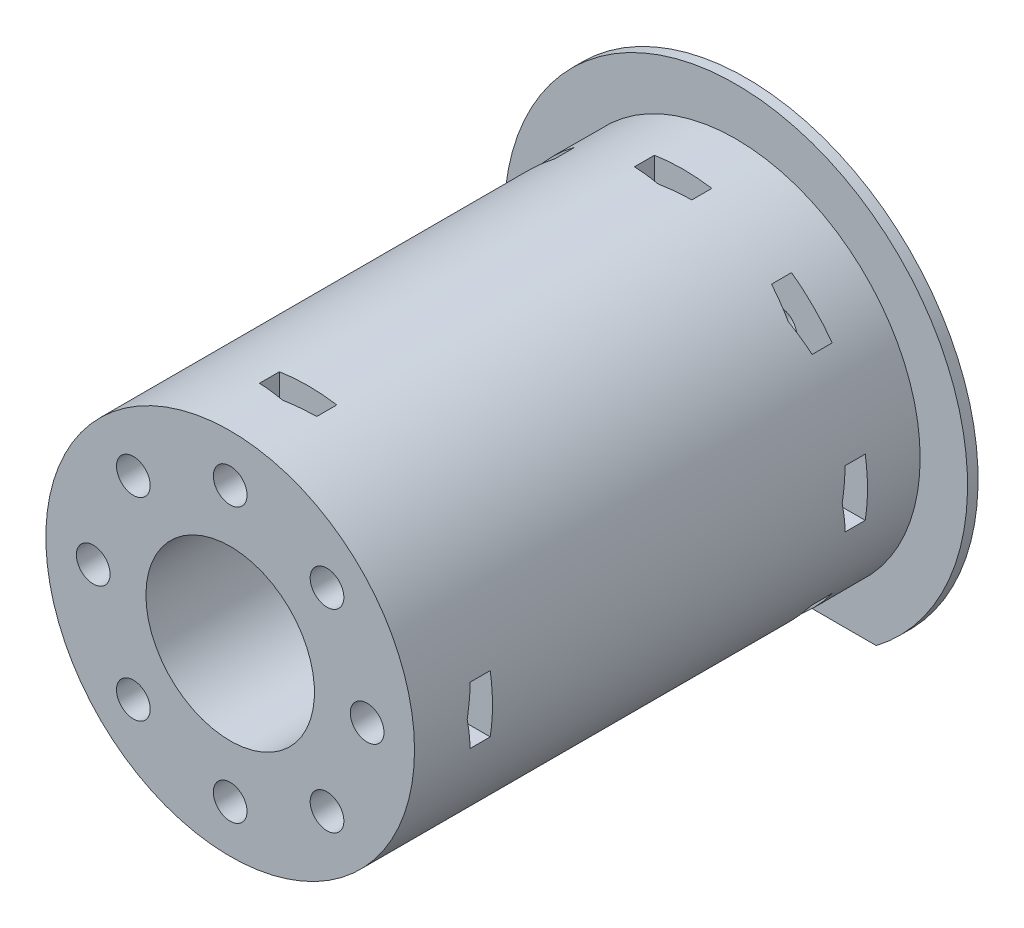
SolidWorks part; units mm, degrees
ref_plane "Front Plane" through (0, 0, 0) normal (1, 0, 0) x (0, 1, 0)
ref_plane "Top Plane" through (0, 0, 0) normal (0, 0, 1) x (0, 1, 0)
ref_plane "Right Plane" through (0, 0, 0) normal (0, 1, 0) x (-1, 0, 0)
sketch "Sketch1" plane through (0, 0, 0) normal (0, 0, 1) x (0, 1, 0)
  circle A0 centre (0, 0) radius 17.5
  dimension "D1" = 35
extrude "Boss-Extrude1" add sketch "Sketch1" along normal blind 24 and the other way blind 24
sketch "Sketch3" plane through (0, 0, -24) normal (0, 0, -1) x (1, 0, 0)
  circle A0 centre (0, 0) radius 22
  dimension "D1" = 44
extrude "Boss-Extrude2" add sketch "Sketch3" along normal blind 1
sketch "Sketch2" plane through (0, 0, 24) normal (0, 0, 1) x (1, 0, 0)
  line L0 (-2.725, 15.725) -> (-2.725, 17.2865)
  line L2 (-2.725, 15.725) -> (-2.725, 10.275)
  line L3 (-2.725, 10.275) -> (2.725, 10.275)
  line L4 (2.725, 15.725) -> (2.725, 10.275)
  line L5 (-2.725, 15.725) -> (2.725, 10.275) construction
  line L6 (-2.725, 10.275) -> (2.725, 15.725) construction
  line L7 (2.725, 15.725) -> (2.725, 17.2865)
  circle A0 centre (0, 0) radius 13 construction
  circle A1 centre (0, 13) radius 1.6
  circle A2 centre (0, 0) radius 17.5 construction
  arc A3 (-2.725, 17.2865) -> (2.725, 17.2865) centre (0, 0) cw
  dimension "D1" = 26
  dimension "D4" = 3.2
  dimension "D2" = 5.45
  dimension "D3" = 5.45
extrude "Cut-Extrude1" cut sketch "Sketch2" against normal through all contours A1
extrude "Cut-Extrude2" cut sketch "Sketch2<4>" against normal blind 2.4 from offset 5 offset against normal yes
sketch "Sketch2<4>" plane through (0, 0, 24) normal (0, 0, 1) x (1, 0, 0) same geometry as "Sketch2"
extrude "Cut-Extrude3" cut sketch "Sketch2<5>" along normal blind 2.4 from offset 43 offset against normal yes
sketch "Sketch2<5>" plane through (0, 0, 24) normal (0, 0, 1) x (1, 0, 0) same geometry as "Sketch2"
chamfer "Chamfer1" distance 2.725 distance2 0.5 2 edges at (-2.725, 13.7808, 19) (2.725, 13.7808, 19) first distance on face at (1.6, 13, 19)
chamfer "Chamfer2" distance 2.725 distance2 0.5 2 edges at (-2.725, 13.7808, -16.6) (2.725, 13.7808, -16.6) first distance on face at (0, 13.8341, -16.6)
pattern_circular "CirPattern1" count 4 over 360 about axis through (0, 0, -24) along (0, 0, 1) of "Cut-Extrude2", "Chamfer1" reverse direction yes
pattern_circular "CirPattern3" count 8 over 360 about axis through (0, 0, -24) along (0, 0, 1) of "Cut-Extrude3", "Chamfer2", "Cut-Extrude1"
sketch "Sketch4" plane through (0, 0, -25) normal (0, 0, -1) x (1, 0, 0)
  circle A0 centre (0, 0) radius 8
  dimension "D1" = 16
extrude "Cut-Extrude4" cut sketch "Sketch4" against normal through all both and the other way through all
sketch "Sketch5" plane through (0, 0, -25) normal (0, 0, -1) x (1, 0, 0)
  line L0 (-0.5, -10) -> (-0.5, -0.5)
  line L1 (-10, 0.5) -> (-0.5, 0.5)
  line L2 (-10, 0.5) -> (-10, -0.5)
  line L3 (-10, -0.5) -> (-0.5, -0.5)
  line L4 (10, 0.5) -> (10, -0.5)
  line L5 (-10, 0.5) -> (10, -0.5) construction
  line L6 (-10, -0.5) -> (10, 0.5) construction
  line L7 (-0.5, -10) -> (0.5, -10)
  line L8 (0.5, -10) -> (0.5, -0.5)
  line L9 (-0.5, 10) -> (0.5, 10)
  line L10 (-0.5, -10) -> (0.5, 10) construction
  line L11 (0.5, -10) -> (-0.5, 10) construction
  line L14 (-0.5, 0.5) -> (-0.5, 10)
  line L15 (0.5, 0.5) -> (0.5, 10)
  line L16 (0.5, 0.5) -> (10, 0.5)
  line L19 (0.5, -0.5) -> (10, -0.5)
  point P0 (0, 0)
  point P6 (0, 0)
  dimension "D1" = 1
  dimension "D2" = 20
  dimension "D3" = 1
  dimension "D4" = 20
extrude "Cut-Extrude5" cut sketch "Sketch5" against normal blind 0.2
sketch "Sketch6" plane through (0, 0, -25) normal (0, 0, -1) x (1, 0, 0)
  line L0 (0, 17.5) -> (-13.3323, 17.5)
  line L1 (0, 17.5) -> (13.3323, 17.5)
  circle A0 centre (0, 0) radius 17.5 construction
  circle A1 centre (0, 0) radius 17.5 construction
  circle A2 centre (0, 0) radius 22 construction
  arc A3 (13.3323, 17.5) -> (-13.3323, 17.5) centre (0, 0) ccw
extrude "Cut-Extrude6" cut sketch "Sketch6" against normal blind 1
